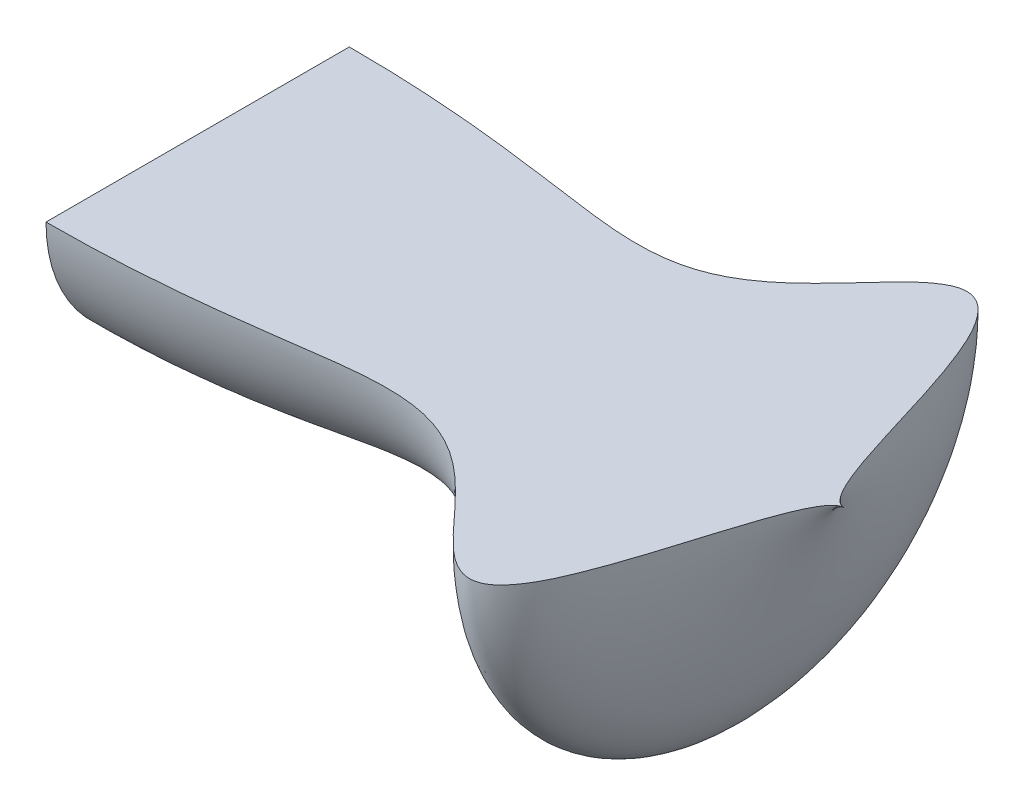
SolidWorks part; units mm, degrees
ref_plane "Front Plane" through (0, 0, 0) normal (0, 0, 1) x (1, 0, 0)
ref_plane "Top Plane" through (0, 0, 0) normal (0, 1, 0) x (1, 0, 0)
ref_plane "Right Plane" through (0, 0, 0) normal (1, 0, 0) x (0, 0, -1)
sketch "Sketch2" plane through (0, 0, 0) normal (0, 1, 0) x (1, 0, 0)
  line L0 (0, 0) -> (0, 29.9104)
  line L1 (0, 29.9104) -> (127.44, 29.9104)
  spline S0 degree 4 poles (-12.8247, 0.3008) (-10.8625, 0.2255) (-8.6622, 0.1005) (-1.7038, -0.016) (2.2115, -0.0111) (11.3056, 0.1636) (16.8375, 0.5223) (24.6164, 1.0544) (31.0208, 1.7658) (38.2225, 2.6228) (44.928, 3.6083) (53.3414, 4.7646) (61.5946, 5.6273) (70.5241, 5.0359) (80.1918, 0.5631) (87.3419, -6.2562) (92.9752, -12.8398) (98.1714, -17.9821) (102.3303, -19.4185) (105.3446, -18.7254) (109.1317, -15.1283) (112.6468, -7.5579) (115.4416, 0.4913) (117.8357, 8.5999) (119.7329, 14.665) (120.8288, 18.1496) (121.8526, 21.0976) (122.7784, 23.5518) (123.6137, 25.4786) (124.3222, 26.91) (125.0103, 28.0865) (125.7295, 28.9998) (126.3448, 29.5521) (126.8289, 29.8115) (127.2475, 29.9042) (127.5045, 29.9205) (127.828, 29.8635) (128.2593, 29.7082) (128.6611, 29.397) (129.05, 28.9915) (129.4108, 28.5131) (130.0815, 27.4388) (130.8724, 25.6686) (131.7172, 23.2099) (132.5867, 20.0586) (133.1573, 17.6773) (133.5119, 16.0823) (133.6846, 15.2845) knots 0 0 0 0 0 0.032265 0.064529 0.09971 0.134891 0.170072 0.205253 0.240434 0.275615 0.310796 0.345976 0.410148 0.445329 0.487974 0.558336 0.607035 0.623025 0.633249 0.644788 0.66642 0.726252 0.799981 0.818413 0.836846 0.855278 0.87371 0.881764 0.889818 0.897872 0.905926 0.909473 0.91302 0.914832 0.916644 0.91729 0.919528 0.921765 0.924791 0.927817 0.930843 0.933869 0.950402 0.966934 0.983467 1 1 1 1 1 construction
  spline S1 degree 4 poles (0, 0) (1.4807, 0) (4.3407, 0.0298) (11.3056, 0.1636) (16.8375, 0.5223) (24.6164, 1.0544) (31.0208, 1.7658) (38.2225, 2.6228) (44.928, 3.6083) (53.3414, 4.7646) (61.5946, 5.6273) (70.5241, 5.0359) (80.1918, 0.5631) (87.3419, -6.2562) (92.9752, -12.8398) (98.1714, -17.9821) (102.3303, -19.4185) (105.3446, -18.7254) (109.1317, -15.1283) (112.6468, -7.5579) (115.4416, 0.4913) (117.8357, 8.5999) (119.7329, 14.665) (120.8288, 18.1496) (121.8526, 21.0976) (122.7784, 23.5518) (123.6137, 25.4786) (124.3222, 26.91) (125.0103, 28.0865) (125.7295, 28.9998) (126.3448, 29.5521) (126.8289, 29.8115) (127.2129, 29.8966) (127.3637, 29.9108) (127.44, 29.9104) knots 0.064529 0.064529 0.064529 0.064529 0.064529 0.09971 0.134891 0.170072 0.205253 0.240434 0.275615 0.310796 0.345976 0.410148 0.445329 0.487974 0.558336 0.607035 0.623025 0.633249 0.644788 0.66642 0.726252 0.799981 0.818413 0.836846 0.855278 0.87371 0.881764 0.889818 0.897872 0.905926 0.909473 0.91302 0.914832 0.916644 0.916644 0.916644 0.916644 0.916644
  dimension "D1" = 127.44
revolve "Revolve3" add sketch "Sketch2" angle 180 about L1 region at (64.6492, 0, -13.5086)
